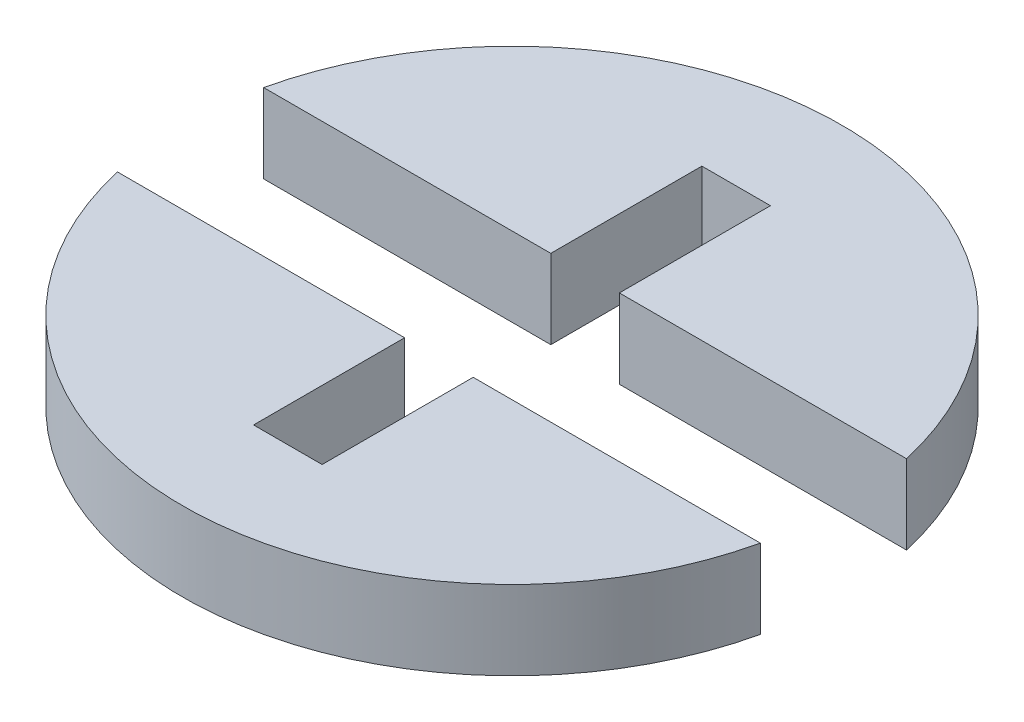
SolidWorks part; units mm, degrees
ref_plane "Front Plane" through (0, 0, 0) normal (0, 0, 1) x (1, 0, 0)
ref_plane "Top Plane" through (0, 0, 0) normal (0, 1, 0) x (1, 0, 0)
ref_plane "Right Plane" through (0, 0, 0) normal (1, 0, 0) x (0, 0, -1)
sketch "Sketch1" plane through (0, 0, 0) normal (0, 1, 0) x (1, 0, 0)
  line L0 (0, -12.5) -> (0, 12.5) construction
  line L1 (0, -12.5) -> (0, 12.5) construction
  line L3 (-1.3, 8.5) -> (1.3, 8.5)
  line L4 (-1.3, 8.5) -> (-1.3, -8.5)
  line L5 (-1.3, -8.5) -> (1.3, -8.5)
  line L6 (1.3, 8.5) -> (1.3, -8.5)
  line L7 (0, -8.5) -> (0, 8.5) construction
  line L8 (-1.3, 0) -> (1.3, 0) construction
  circle A0 centre (0, 0) radius 12.5
extrude "Boss-Extrude1" add sketch "Sketch1" along normal blind 1.5 and the other way blind 1.5
sketch "Sketch4" plane through (0, 0, 0) normal (1, 0, 0) x (0, 0, -1)
  line L0 (8.5, -1.3) -> (8.5, 1.3) construction
  line L1 (2.7713, -1.6) -> (2.7713, 1.6)
  line L2 (2.7713, 1.6) -> (0, 3.2)
  line L3 (0, 3.2) -> (-2.7713, 1.6)
  line L4 (-2.7713, 1.6) -> (-2.7713, -1.6)
  line L5 (-2.7713, -1.6) -> (0, -3.2)
  line L6 (0, -3.2) -> (2.7713, -1.6)
  circle A0 centre (0, 0) radius 2.7713 construction
  dimension "D1" = 3.2
extrude "Cut-Extrude1" cut sketch "Sketch4" against normal through all both and the other way through all
